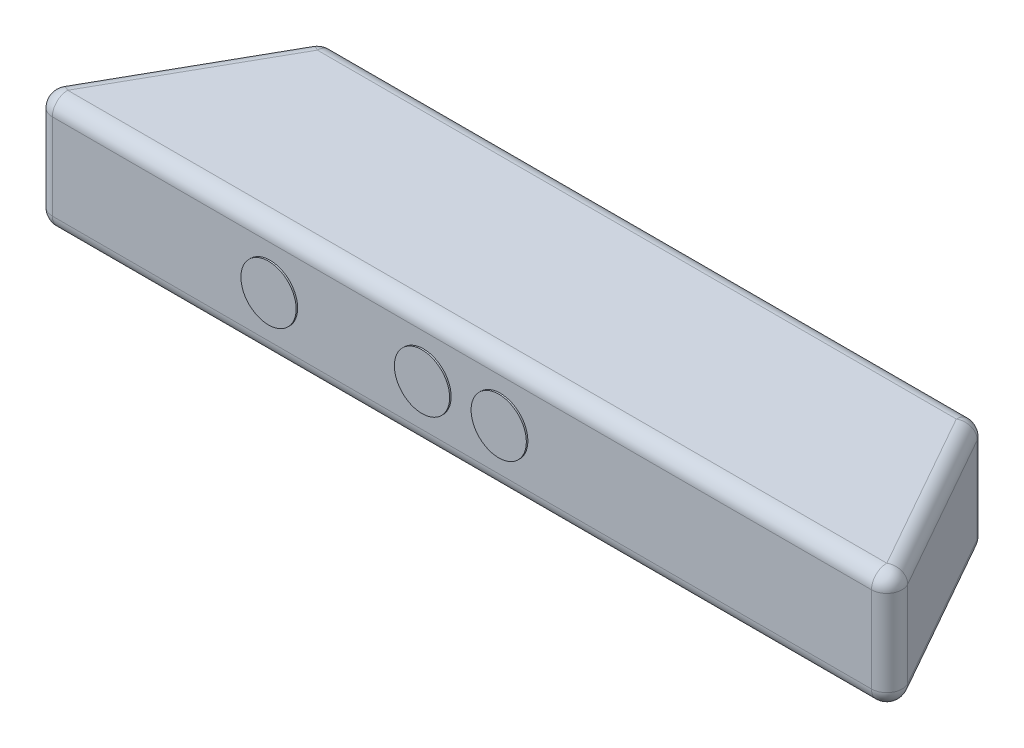
SolidWorks part; units mm, degrees
material "ABS"
ref_plane "Front Plane" through (0, 0, 0) normal (0, 0, 1) x (1, 0, 0)
ref_plane "Top Plane" through (0, 0, 0) normal (0, 1, 0) x (1, 0, 0)
ref_plane "Right Plane" through (0, 0, 0) normal (1, 0, 0) x (0, 0, -1)
sketch "Sketch1" plane through (0, 0, 0) normal (0, 1, 0) x (1, 0, 0)
  line L0 (-142, 0) -> (142, 0)
  line L1 (142, 0) -> (107, 62)
  line L2 (107, 62) -> (-107, 62)
  line L3 (-107, 62) -> (-142, 0)
  line L4 (0, 0) -> (0, 62) construction
  dimension "D1" = 62
  dimension "D2" = 284
  dimension "D3" = 214
extrude "Boss-Extrude1" add sketch "Sketch1" along normal blind 38
sketch "Sketch2" plane through (0, 0, 0) normal (0, -1, 0) x (1, 0, 0)
  line L0 (0, 0) -> (0, -62) construction
  line L1 (107, -62) -> (-107, -62) construction
  line L2 (8.5, -31) -> (-8.5, -31) construction
  line L3 (0, -35.75) -> (0, -31) construction
  arc A0 (8.5, -31) -> (-8.5, -31) centre (0, -25.7697) cw
  arc A1 (8.5, -31) -> (-8.5, -31) centre (0, -36.2303) ccw
  dimension "D1" = 4.75
  dimension "D2" = 17
extrude "Boss-Extrude2" add sketch "Sketch2" along normal blind 10
fillet "Fillet1" radius 5 12 edges at (-142, 19, 0) (-124.5, 38, -31) (-107, 19, -62) (-124.5, 0, -31) (0, 0, -62) (0, 38, -62) (0, 38, 0) (124.5, 38, -31) (107, 19, -62) (142, 19, 0) (124.5, 0, -31) (0, 0, 0)
sketch "Sketch3" plane through (0, 0, 0) normal (0, 0, 1) x (1, 0, 0)
  line L0 (0, 5) -> (0, 33) construction
  line L1 (-133.4357, 5) -> (133.4357, 5) construction
  line L2 (133.4357, 33) -> (-133.4357, 33) construction
  line L3 (-133.4357, 19) -> (133.4357, 19) construction
  line L4 (-133.4357, 33) -> (-133.4357, 5) construction
  line L5 (133.4357, 5) -> (133.4357, 33) construction
  circle A0 centre (12.5, 19) radius 9
  circle A1 centre (-12.5, 19) radius 9
  circle A2 centre (-62.5, 19) radius 9
  dimension "D1" = 18
  dimension "D2" = 25
  dimension "D3" = 50
extrude "Cut-Extrude1" cut sketch "Sketch3" against normal blind 5
sketch "Sketch5" plane through (0, 0, 0) normal (0, 0, 1) x (1, 0, 0)
  circle A0 centre (-12.5, 19) radius 9 construction
  circle A1 centre (12.5, 19) radius 9 construction
  circle A2 centre (-62.5, 19) radius 9 construction
  circle A3 centre (-12.5, 19) radius 9
  circle A4 centre (12.5, 19) radius 9
  circle A5 centre (-62.5, 19) radius 9
  circle A6 centre (-12.5, 19) radius 9
  circle A7 centre (12.5, 19) radius 9
  circle A8 centre (-62.5, 19) radius 9
  circle M3 centre (12.5, 19) radius 9
extrude "Boss-Extrude3" add sketch "Sketch5" against normal mid plane 1 contours M3 | A5 | A3 region at (12.5, 19, 0)
sketch "Sketch6" plane through (0, 0, 0) normal (0, -1, 0) x (1, 0, 0)
  line L0 (0, -5) -> (0, -57) construction
  line L1 (133.4357, -5) -> (-133.4357, -5) construction
  line L2 (-104.0809, -57) -> (104.0809, -57) construction
  line L3 (-133.4357, 0) -> (133.4357, 0) construction
  circle A0 centre (-97, -17.5) radius 3
  circle A1 centre (97, -17.5) radius 3
  dimension "D3" = 6
  dimension "D1" = 17.5
  dimension "D2" = 97
extrude "Cut-Extrude2" cut sketch "Sketch6" against normal blind 2.5
